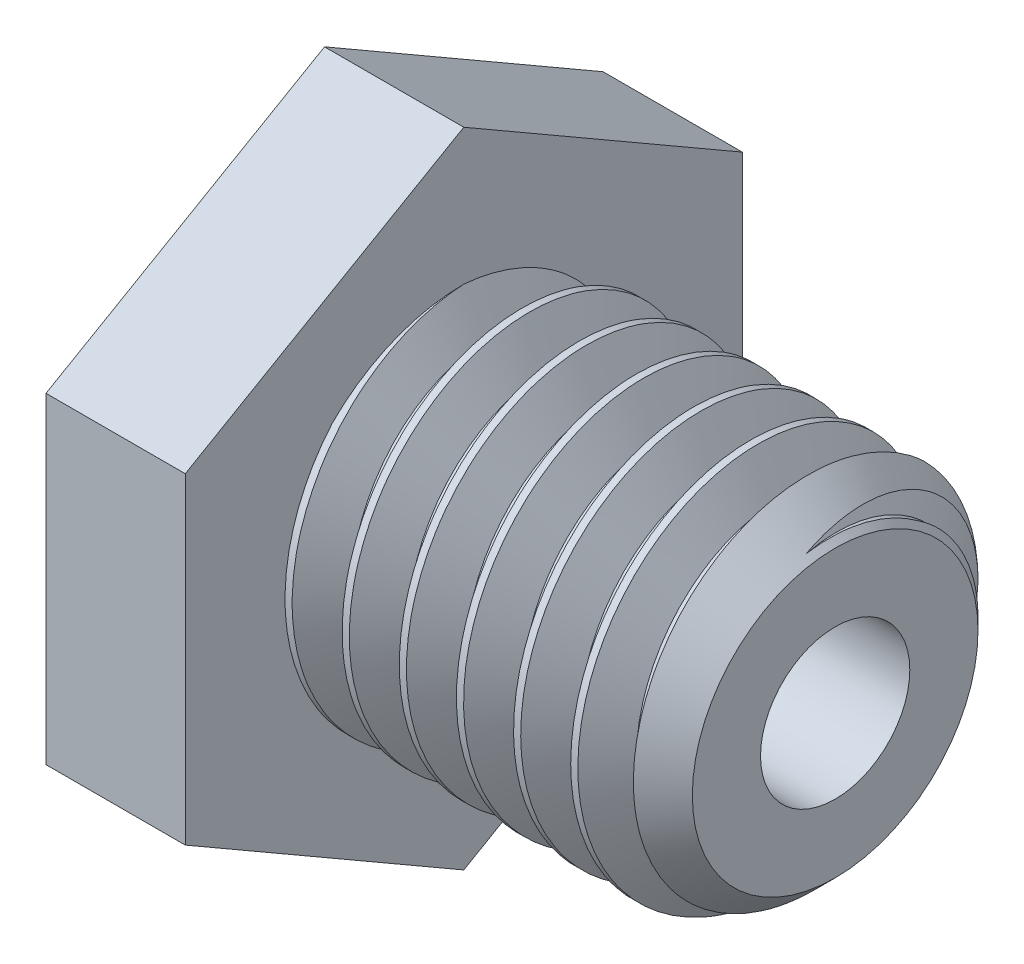
SolidWorks part; units mm, degrees
material "PVC Rigid"
ref_plane "Front Plane" through (0, 0, 0) normal (0, 0, 1) x (1, 0, 0)
ref_plane "Top Plane" through (0, 0, 0) normal (0, 1, 0) x (1, 0, 0)
ref_plane "Right Plane" through (0, 0, 0) normal (1, 0, 0) x (0, 0, -1)
sketch "Sketch1" plane through (0, 0, 0) normal (0, 0, 1) x (1, 0, 0)
  line L0 (-17.8594, 0) -> (17.8594, 0) construction
  line L1 (17.8594, 6.35) -> (17.8594, -6.35) construction
  line L2 (-7.5406, 9.525) -> (-7.5406, -9.525) construction
  line L3 (-17.8594, 9.525) -> (-17.8594, -9.525) construction
  point P9 (-7.5406, 0)
  point P10 (11.0209, -6.35)
  dimension "Screw Dia" = 12.7
  dimension "Hex" = 19.05
  dimension "Head Ht" = 10.3187
  dimension "Screw Lenght" = 25.4
  dimension "D1" = 6.8385
ref_plane "Plane2" through (17.8594, 0, 0) normal (1, 0, 0) x (0, 0, -1)
sketch "Sketch5" plane through (17.8594, 0, 0) normal (1, 0, 0) x (0, 0, -1)
  circle A0 centre (0, 0) radius 6.35
extrude "Boss-Extrude3" add sketch "Sketch5" against normal up to vertex (25.4 mm away) up to point (-7.5406, 0, 0)
sketch "Sketch9" plane through (17.8594, 0, 0) normal (1, 0, 0) x (0, 0, -1)
  circle A1 centre (0, 0) radius 6.35
  circle A2 centre (0, 0) radius 6.35
  dimension "D1" = 0
curve "Helix/Spiral1" pitch 1.9538 height 27.3538 turns 14 parameters "Pitch"=1.9538
chamfer "Chamfer1" distance 1.4654 angle 45 1 edges at (17.8594, 0, -6.35)
sketch "Sketch10" plane through (0, 0, 0) normal (0, 0, 1) x (1, 0, 0)
  line L0 (17.8594, 6.35) -> (18.5921, 5.0809)
  line L1 (18.5921, 5.0809) -> (18.8363, 5.0809)
  line L2 (18.8363, 5.0809) -> (19.569, 6.35)
  line L3 (17.8594, 6.35) -> (19.569, 6.35)
  line L4 (18.7142, 6.35) -> (18.7142, 5.0809) construction
  line L5 (18.2257, 5.7155) -> (19.2026, 5.7155) construction
  dimension "D1" = 60
  dimension "D2" = 0.2442
  dimension "D3" = 0.9769
sweep "Cut-Sweep1" cut profiles "Sketch10" path "Helix/Spiral1" align with end faces yes
sketch "Sketch6" plane through (-7.5406, 0, 0) normal (-1, 0, 0) x (0, 0, 1)
  line L0 (0, 9.525) -> (0, -9.525) construction
  line L1 (9.525, 5.4993) -> (0, 10.9985)
  line L2 (0, 10.9985) -> (-9.525, 5.4993)
  line L3 (-9.525, 5.4993) -> (-9.525, -5.4993)
  line L4 (-9.525, -5.4993) -> (0, -10.9985)
  line L5 (0, -10.9985) -> (9.525, -5.4993)
  line L6 (9.525, -5.4993) -> (9.525, 5.4993)
  circle A0 centre (0, 0) radius 9.525 construction
extrude "Boss-Extrude4" add sketch "Sketch6" along normal up to vertex (10.3187 mm away) up to point (-17.8594, -9.525, 0)
sketch "Sketch7" plane through (-17.8594, 0, 0) normal (-1, 0, 0) x (0, 0, 1)
  circle A0 centre (0, 0) radius 9.525 construction
  circle A1 centre (0, 0) radius 9.525
sketch "Sketch8" plane through (-17.8594, 0, 0) normal (-1, 0, 0) x (0, 0, 1)
  circle A0 centre (0, 0) radius 9.525 construction
  circle A1 centre (0, 0) radius 9.525
extrude "Cut-Extrude3" cut sketch "Sketch8" against normal through all draft 60 flip side to cut
sketch "Sketch11" plane through (0, 0, 0) normal (0, 0, 1) x (1, 0, 0)
  line L0 (-1000, 0) -> (49000, 0) construction
  line L1 (5.1594, 0) -> (5.1594, 4.8846)
  line L2 (5.1594, 4.8846) -> (2.3996, 7.6444)
  line L3 (2.3996, 7.6444) -> (2.3996, 8.9261)
  line L4 (2.3996, 8.9261) -> (25.9691, 8.9261)
  line L5 (25.9691, 8.9261) -> (25.9691, 0)
  line L6 (25.9691, 0) -> (5.1594, 0)
  line L7 (-7.5406, 5.4993) -> (-7.5406, 10.9985) construction
  dimension "D1" = 12.7
  dimension "D2" = 135
revolve "Cut-Revolve1" cut sketch "Sketch11" angle 360 about L0
sketch "Sketch12" plane through (0, 0, 0) normal (0, 0, 1) x (1, 0, 0)
  line L0 (-7.5406, 5.4993) -> (-7.5406, 10.9985) construction
  line L1 (-30.1105, 17.8378) -> (-12.3031, 17.8378)
  line L2 (-30.1105, 17.8378) -> (-30.1105, -14.799)
  line L3 (-30.1105, -14.799) -> (-12.3031, -14.799)
  line L4 (-12.3031, 17.8378) -> (-12.3031, -14.799)
  dimension "D1" = 4.7625
extrude "Cut-Extrude4" cut sketch "Sketch12" against normal through all both and the other way through all
hole_wizard "1/4-20 Tapped Hole1" positions "Sketch13" profile "Sketch14" tap size "1/4-20" standard "ANSI Inch" end condition through all
sketch "Sketch13" plane through (-12.3031, 0, 0) normal (-1, 0, 0) x (0, 0, 1)
  point P0 (0, 0)
sketch "Sketch14" plane through (-12.3031, 0, 0) normal (0, 1, 0) x (0, 0, 1)
  line L0 (0, 0) -> (0, 18.0778)
  line L1 (0, 18.0778) -> (2.5527, 18.0778)
  line L2 (2.5527, 18.0778) -> (2.5527, 0)
  line L5 (2.5527, 0) -> (0, 0)
  line L11 (0, -6.35) -> (0, 107.95) construction
  dimension "Thru Tap Drill Dia." = 5.1054
  dimension "Thru Tap Drill Depth" = 18.0778
cosmetic thread "Hole Thread1" parameters "D2"=6.35
equation "\"D2@Sketch10\" = \"Pitch@Helix/Spiral1\"*.125"
equation "\"D3@Sketch10\" = \"Pitch@Helix/Spiral1\"*.5"
equation "\"D3@Helix/Spiral1\" = \"Screw Lenght@Sketch1\"+\"Pitch@Helix/Spiral1\""
equation "\"D1@Chamfer1\" = \"Pitch@Helix/Spiral1\"*.75"
equation "\"D1@Sketch1\" = \"Pitch@Helix/Spiral1\"*3.5"
